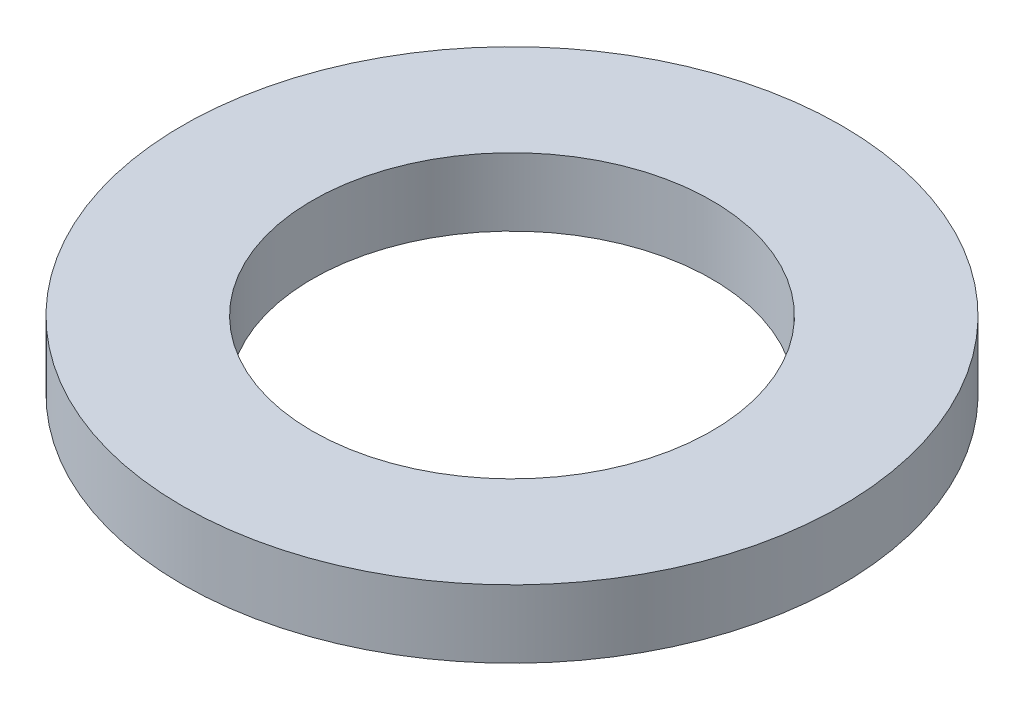
SolidWorks part; units mm, degrees
ref_plane "Front Plane" through (0, 0, 0) normal (0, 0, 1) x (1, 0, 0)
ref_plane "Top Plane" through (0, 0, 0) normal (0, 1, 0) x (1, 0, 0)
ref_plane "Right Plane" through (0, 0, 0) normal (1, 0, 0) x (0, 0, -1)
sketch "Sketch1" plane through (0, 0, 0) normal (0, 1, 0) x (1, 0, 0)
  circle A0 centre (0, 0) radius 82.5
  dimension "FLANGE_OD" = 165
extrude "Boss-Extrude1" add sketch "Sketch1" along normal blind 17
sketch "Sketch2" plane through (0, 0, 0) normal (0, 1, 0) x (1, 0, 0)
  circle A0 centre (0, 0) radius 50
  dimension "BORE_D" = 100
extrude "Cut-Extrude1" cut sketch "Sketch2" along normal through all
sketch "Sketch3" plane through (0, 17, 0) normal (0, 1, 0) x (1, 0, 0)
  circle A0 centre (0, 0) radius 29.2544 construction
  circle A1 centre (-29.2544, 0) radius 3.139
  dimension "BOLT_D" = 6.278
  dimension "BOLT_PCD" = 58.5087
extrude "Cut-Extrude2" cut sketch "Sketch3" against normal blind 12.5155 rebuild error yes
pattern_circular "CirPattern1" count 3 over 360 rebuild error yes
